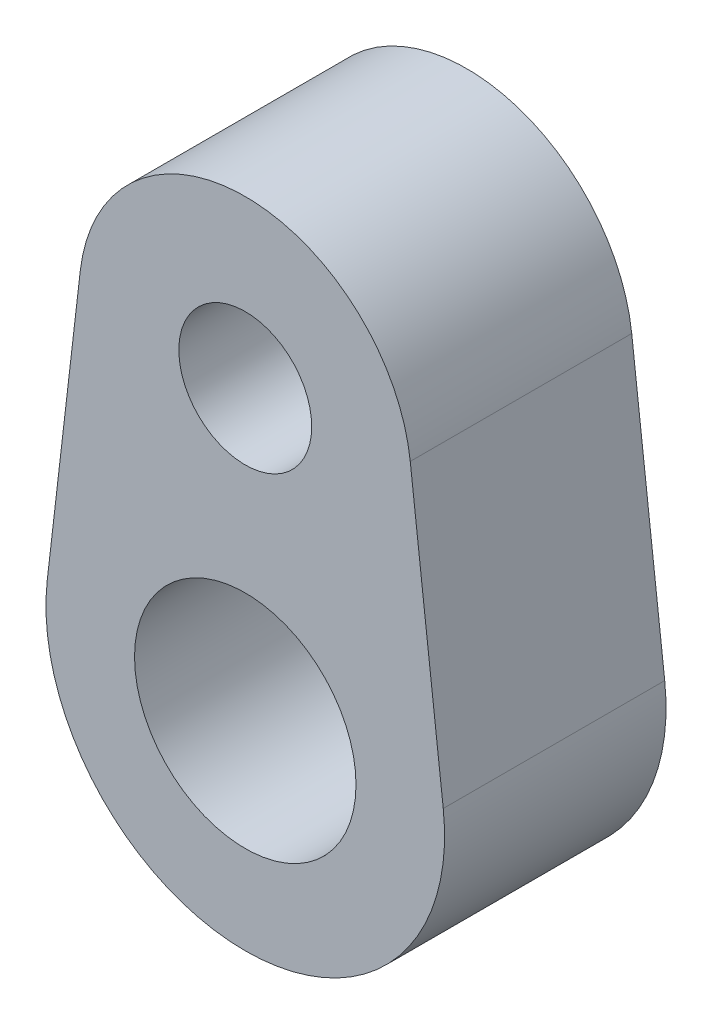
SolidWorks part; units mm, degrees
ref_plane "前视基准面" through (0, 0, 0) normal (0, 0, 1) x (1, 0, 0)
ref_plane "上视基准面" through (0, 0, 0) normal (0, 1, 0) x (1, 0, 0)
ref_plane "右视基准面" through (0, 0, 0) normal (1, 0, 0) x (0, 0, -1)
sketch "草图1" plane through (0, 0, 0) normal (0, 0, 1) x (1, 0, 0)
  line L0 (0, -55) -> (0, 55) construction
  line L1 (8.9399, 1.0385) -> (7.4499, 13.8654)
  line L2 (-7.4499, 13.8654) -> (-8.9399, 1.0385)
  arc A0 (-8.9399, 1.0385) -> (8.9399, 1.0385) centre (0, 0) ccw
  arc A1 (7.4499, 13.8654) -> (-7.4499, 13.8654) centre (0, 13) ccw
  circle A2 centre (0, 13) radius 3
  circle A3 centre (0, 0) radius 5
  arc A4 (5.0467, 7.4519) -> (-5.0467, 7.4519) centre (0, 0) ccw construction
  arc A5 (-5.0467, 7.4519) -> (5.0467, 7.4519) centre (0, 13) ccw construction
  arc A6 (-5.0467, 7.4519) -> (-8.9399, 1.0385) centre (0, 0) ccw construction
  arc A7 (-7.4499, 13.8654) -> (-5.0467, 7.4519) centre (0, 13) ccw construction
  arc A8 (5.0467, 7.4519) -> (7.4499, 13.8654) centre (0, 13) ccw construction
  arc A9 (8.9399, 1.0385) -> (5.0467, 7.4519) centre (0, 0) ccw construction
  dimension "D1" = 18
  dimension "D2" = 15
  dimension "D4" = 6
  dimension "D5" = 10
  dimension "D3" = 13
extrude "凸台-拉伸1" add sketch "草图1" along normal mid plane 10
sketch "草图2" plane through (0, 0, 0) normal (0, 0, 1) x (1, 0, 0)
  line L0 (0, 0) -> (-12.7679, 12.7679) construction
  line L1 (5.5, 0) -> (-5.5, 0) construction
  dimension "D1" = 45
ref_plane "基准面1" through (-12.7679, 12.7679, 0) normal (-0.7071, 0.7071, 0) x (0.7071, 0.7071, 0)
hole_wizard "M5 螺纹孔1" positions "草图3" profile "草图4" tap size "M5" standard "GB" end condition up to next
sketch "草图3" plane through (-12.7679, 12.7679, 0) normal (-0.7071, 0.7071, 0) x (0.7071, 0.7071, 0)
  point P0 (0, 0)
sketch "草图4" plane through (-12.7679, 12.7679, 0) normal (0, 0, 1) x (-0.7071, -0.7071, 0)
  line L0 (0, 0) -> (0, 13.0565)
  line L1 (0, 13.0565) -> (2.525, 13.0565)
  line L2 (2.1, 12.6315) -> (2.1, 0)
  line L5 (2.1, 0) -> (0, 0)
  line L7 (2.525, 13.0565) -> (2.1, 12.6315)
  line L8 (-2.525, 13.0565) -> (-2.1, 12.6315) construction
  line L11 (0, -6.35) -> (0, 107.95) construction
  dimension "通孔螺纹孔钻头直径" = 4.2
  dimension "通孔螺纹孔钻头深度" = 13.0565
  dimension "远端锥形沉头孔直径" = 5.05
  dimension "远端锥形沉头孔角度" = 90
cosmetic thread "孔螺纹线1" parameters "D2"=5
